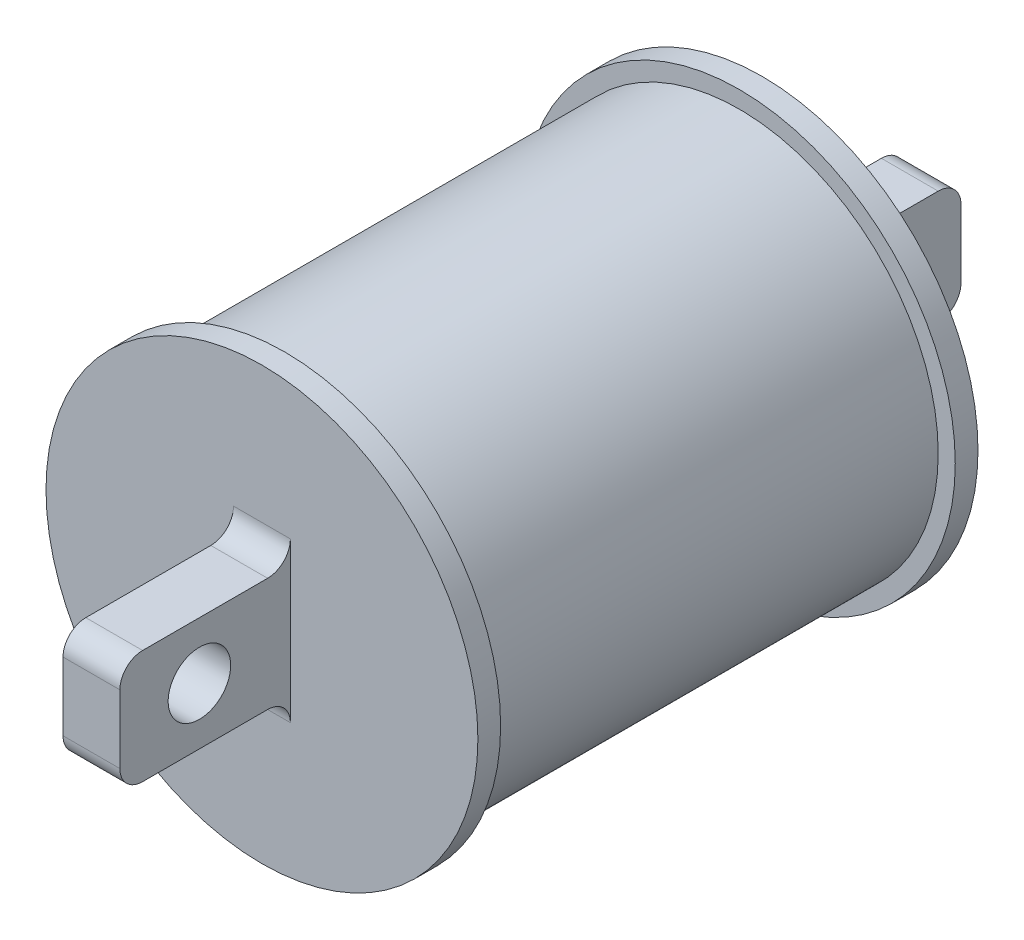
SolidWorks part; units mm, degrees
ref_plane "Front Plane" through (0, 0, 0) normal (0, 0, 1) x (1, 0, 0)
ref_plane "Top Plane" through (0, 0, 0) normal (0, 1, 0) x (1, 0, 0)
ref_plane "Right Plane" through (0, 0, 0) normal (1, 0, 0) x (0, 0, -1)
sketch "Sketch1" plane through (0, 0, 0) normal (0, 0, 1) x (1, 0, 0)
  circle A0 centre (0, 0) radius 22.225
  dimension "D1" = 44.45
extrude "Boss-Extrude1" add sketch "Sketch1" along normal mid plane 50.8
sketch "Sketch2" plane through (0, 0, 25.4) normal (0, 0, 1) x (1, 0, 0)
  circle A0 centre (0, 0) radius 24.13
  dimension "D1" = 48.26
extrude "Boss-Extrude2" add sketch "Sketch2" along normal blind 2.54
sketch "Sketch3" plane through (0, 0, 27.94) normal (0, 0, 1) x (1, 0, 0)
  line L1 (-3.175, -6.35) -> (3.175, -6.35)
  line L2 (-3.175, -6.35) -> (-3.175, 6.35)
  line L3 (-3.175, 6.35) -> (3.175, 6.35)
  line L4 (3.175, -6.35) -> (3.175, 6.35)
  line L5 (-3.175, -6.35) -> (3.175, 6.35) construction
  line L6 (-3.175, 6.35) -> (3.175, -6.35) construction
  point P0 (0, 0)
  dimension "D1" = 6.35
  dimension "D2" = 12.7
extrude "Boss-Extrude3" add sketch "Sketch3" along normal blind 19.05
sketch "Sketch4" plane through (3.175, 0, 0) normal (1, 0, 0) x (0, 0, -1)
  line L0 (-38.1, 0) -> (-27.94, 0) construction
  line L1 (-27.94, -6.35) -> (-27.94, 6.35) construction
  line L3 (0, 26.543) -> (0, -26.543) construction
  circle A0 centre (-38.1, 0) radius 3.4925
  dimension "D1" = 6.985
  dimension "D2" = 38.1
extrude "Cut-Extrude1" cut sketch "Sketch4" against normal through all
fillet "Fillet1" radius 2.54 4 edges at (0, -6.35, 27.94) (0, 6.35, 27.94) (0, -6.35, 46.99) (0, 6.35, 46.99)
mirror "Mirror1" about plane through (0, 0, 0) normal (0, 0, 1) of "Fillet1", "Cut-Extrude1", "Boss-Extrude3", "Boss-Extrude2"
